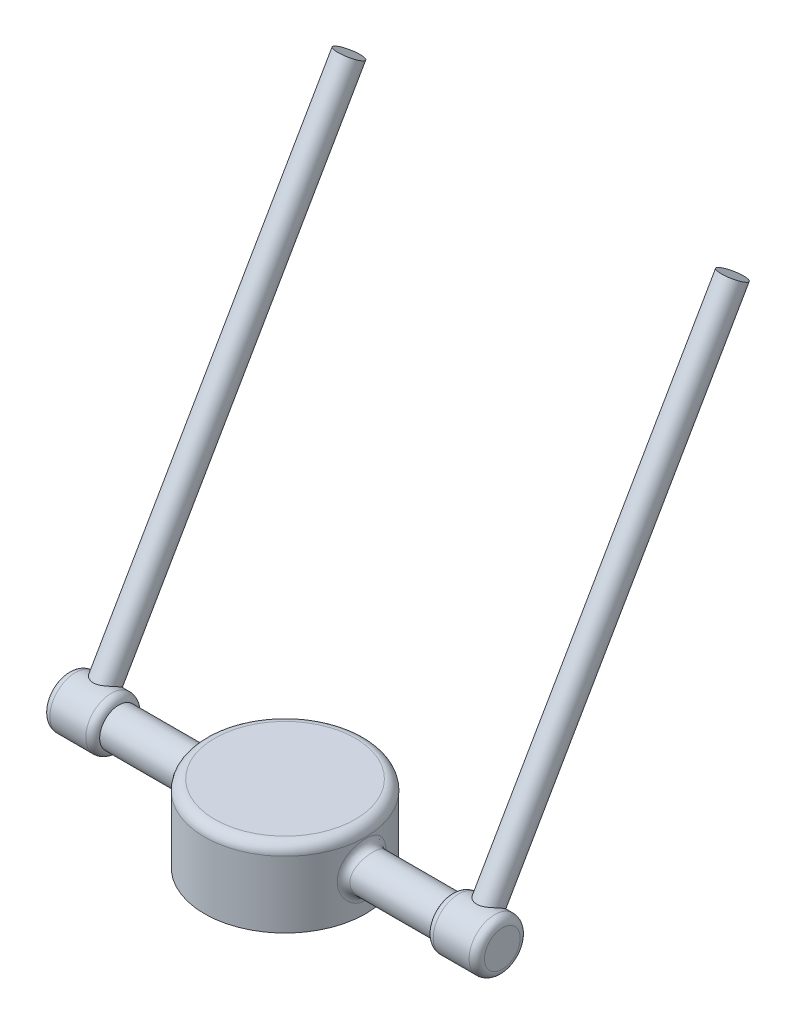
SolidWorks part; units mm, degrees
material "Polyester Resin"
ref_plane "Front Plane" through (0, 0, 0) normal (0, 0, 1) x (1, 0, 0)
ref_plane "Top Plane" through (0, 0, 0) normal (0, 1, 0) x (1, 0, 0)
ref_plane "Right Plane" through (0, 0, 0) normal (1, 0, 0) x (0, 0, -1)
sketch "Sketch1" plane through (0, 0, 0) normal (0, 1, 0) x (1, 0, 0)
  circle A0 centre (0, 0) radius 31.5
  dimension "D1" = 63
extrude "Boss-Extrude1" add sketch "Sketch1" along normal blind 30
sketch "Sketch2" plane through (0, 0, 0) normal (1, 0, 0) x (0, 0, -1)
  line L0 (0, 0) -> (0, 30) construction
  line L1 (31.5, 30) -> (-31.5, 30) construction
  circle A0 centre (0, 15) radius 7.5
  point P6 (0, 0)
  point P9 (0, 16.3513)
  point P10 (0, 0)
  dimension "D1" = 15
extrude "Boss-Extrude2" add sketch "Sketch2" along normal blind 65
sketch "Sketch3" plane through (65, 0, 0) normal (1, 0, 0) x (0, 0, -1)
  circle A0 centre (0, 15) radius 10
  point P3 (0, 0)
  dimension "D1" = 20
extrude "Boss-Extrude3" add sketch "Sketch3" along normal blind 20
ref_axis "Axis1" through (0, 15, 0) along (1, 0, 0)
ref_plane "Plane1" through (0, 11.25, -6.4952) normal (0, -0.866, 0.5) x (1, 0, 0)
sketch "Sketch4" plane through (0, 11.25, -6.4952) normal (0, -0.866, 0.5) x (1, 0, 0)
  line L0 (0, 7.5) -> (65, 7.5) construction
  line L2 (65, 17.5) -> (65, -2.5) construction
  circle A0 centre (75, 7.5) radius 5
  point P2 (0, 0)
  point P3 (0, 0)
  dimension "D1" = 10
  dimension "D2" = 10
extrude "Boss-Extrude4" add sketch "Sketch4" against normal blind 200
fillet "Fillet1" radius 3 3 edges at (30.6305, 16.492, -7.3501) (65, 15, -10) (85, 15, -10)
mirror "Mirror1" about plane through (0, 0, 0) normal (1, 0, 0) of "Boss-Extrude3", "Boss-Extrude4", "Fillet1", "Boss-Extrude2"
fillet "Fillet2" radius 4 1 edges at (0, 30, 31.5)
